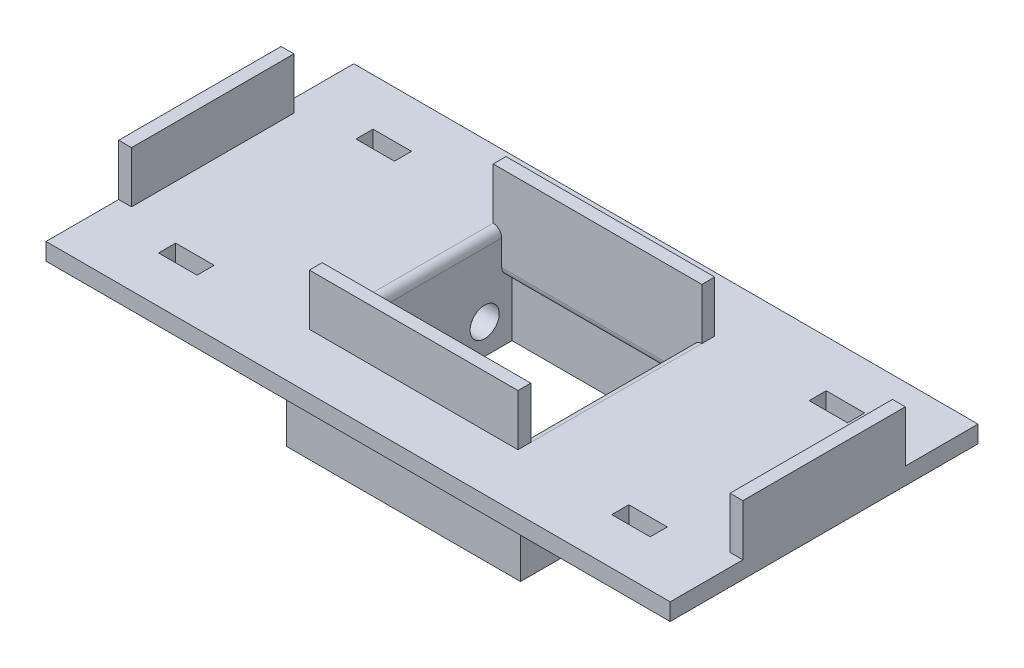
SolidWorks part; units mm, degrees
ref_plane "Front Plane" through (0, 0, 0) normal (0, 0, 1) x (1, 0, 0)
ref_plane "Top Plane" through (0, 0, 0) normal (0, 1, 0) x (1, 0, 0)
ref_plane "Right Plane" through (0, 0, 0) normal (1, 0, 0) x (0, 0, -1)
sketch "Sketch1" plane through (0, 0, 0) normal (0, 1, 0) x (1, 0, 0)
  line L1 (-36.5, 18) -> (36.5, 18)
  line L2 (-36.5, 18) -> (-36.5, -18)
  line L3 (-36.5, -18) -> (36.5, -18)
  line L4 (36.5, 18) -> (36.5, -18)
  line L5 (-36.5, 18) -> (36.5, -18) construction
  line L6 (-36.5, -18) -> (36.5, 18) construction
  point P0 (0, 0)
  dimension "D1" = 36
  dimension "D2" = 73
extrude "Boss-Extrude1" add sketch "Sketch1" along normal blind 2
sketch "Sketch2" plane through (0, 2, 0) normal (0, 1, 0) x (1, 0, 0)
  line L0 (-36.5, 0) -> (36.5, 0) construction
  line L1 (-36.5, 18) -> (-36.5, -18) construction
  line L2 (36.5, -18) -> (36.5, 18) construction
  line L3 (-36.5, 0) -> (-35, 0) construction
  line L4 (-36.5, -9.5) -> (-35, -9.5)
  line L5 (-36.5, -9.5) -> (-36.5, 9.5)
  line L6 (-36.5, 9.5) -> (-35, 9.5)
  line L7 (-35, -9.5) -> (-35, 9.5)
  line L8 (36.5, 9.5) -> (35, 9.5)
  line L9 (36.5, 9.5) -> (36.5, -9.5)
  line L10 (36.5, -9.5) -> (35, -9.5)
  line L11 (35, 9.5) -> (35, -9.5)
  line L12 (35, 0) -> (36.5, 0) construction
  dimension "D1" = 19
  dimension "D2" = 1.5
  dimension "D3" = 1.5
extrude "Boss-Extrude2" add sketch "Sketch2" along normal blind 6
sketch "Sketch3" plane through (0, 0, 0) normal (0, -1, 0) x (1, 0, 0)
  line L0 (-12.2, 11.2) -> (12.2, 11.2)
  line L1 (-13.7, 12.7) -> (13.7, 12.7)
  line L2 (-13.7, 12.7) -> (-13.7, -12.7)
  line L3 (-13.7, -12.7) -> (13.7, -12.7)
  line L4 (13.7, 12.7) -> (13.7, -12.7)
  line L5 (-13.7, 12.7) -> (13.7, -12.7) construction
  line L6 (-13.7, -12.7) -> (13.7, 12.7) construction
  line L7 (12.2, 11.2) -> (12.2, -11.2)
  line L8 (-12.2, -11.2) -> (12.2, -11.2)
  line L9 (-12.2, 11.2) -> (-12.2, -11.2)
  point P0 (0, 0)
  dimension "D1" = 27.4
  dimension "D2" = 25.4
  dimension "D3" = 1.5
extrude "Boss-Extrude3" add sketch "Sketch3" along normal blind 10
sketch "Sketch4" plane through (0, 0, 0) normal (0, -1, 0) x (1, 0, 0)
  line L1 (-12.2, 10) -> (12.2, 10)
  line L2 (-12.2, 10) -> (-12.2, -10)
  line L3 (-12.2, -10) -> (12.2, -10)
  line L4 (12.2, 11.2) -> (-12.2, 11.2)
  line L5 (-12.2, 11.2) -> (-12.2, -11.2)
  line L6 (-12.2, -11.2) -> (12.2, -11.2)
  line L7 (12.2, -11.2) -> (12.2, 11.2)
  line L8 (12.2, 11.2) -> (-12.2, 11.2)
  line L9 (-12.2, 11.2) -> (-12.2, -11.2)
  line L10 (-12.2, -11.2) -> (12.2, -11.2)
  line L11 (12.2, -11.2) -> (12.2, 11.2)
  line L12 (12.2, 10) -> (12.2, -10)
  line L13 (-12.2, 10) -> (12.2, -10) construction
  line L14 (-12.2, -10) -> (12.2, 10) construction
  point P2 (0, 0)
  line M6 (-12.2, 11.2) -> (-12.2, -11.2)
  line M8 (12.2, -11.2) -> (12.2, 11.2)
  dimension "D2" = 20
  dimension "D1" = 0
extrude "Cut-Extrude1" cut sketch "Sketch4" against normal through all contours L3 L1 M6 M8 region at (0, 0, 0)
sketch "Sketch5" plane through (0, 2, 0) normal (0, 1, 0) x (1, 0, 0)
  line L0 (12.2, -10) -> (12.2, 10) construction
  line L1 (-12.2, 10) -> (12.2, 10)
  line L2 (-12.2, 10) -> (-12.2, 11.5)
  line L3 (-12.2, 11.5) -> (12.2, 11.5)
  line L4 (12.2, 10) -> (12.2, 11.5)
  line L5 (-12.2, -10) -> (12.2, -10)
  line L6 (-12.2, -10) -> (-12.2, -11.5)
  line L7 (-12.2, -11.5) -> (12.2, -11.5)
  line L8 (12.2, -10) -> (12.2, -11.5)
  line L9 (-12.2, 10) -> (-12.2, -10) construction
  dimension "D1" = 1.5
  dimension "D2" = 1.5
extrude "Boss-Extrude4" add sketch "Sketch5" along normal blind 6
sketch "Sketch8" plane through (13.7, 0, 0) normal (1, 0, 0) x (0, 0, -1)
  line L0 (0, 0) -> (0, -10) construction
  line L1 (12.7, -10) -> (-12.7, -10) construction
  line L2 (-8, 0) -> (-8, -10) construction
  line L3 (-18, 0) -> (18, 0) construction
  line L4 (8, 0) -> (8, -10) construction
  line L5 (12.7, 0) -> (-12.7, 0) construction
  circle A0 centre (-8, -6.5) radius 1.7
  circle A1 centre (8, -6.5) radius 1.7
  dimension "D3" = 3.4
  dimension "D4" = 3.4
  dimension "D1" = 8
  dimension "D2" = 8
  dimension "D5" = 6.5
  dimension "D6" = 6.5
extrude "Cut-Extrude3" cut sketch "Sketch8" against normal through all
sketch "Sketch9" plane through (0, 2, 0) normal (0, 1, 0) x (1, 0, 0)
  line L0 (-36.5, 11.5) -> (36.5, 11.5) construction
  line L1 (-36.5, 18) -> (-36.5, 9.5) construction
  line L2 (36.5, 9.5) -> (36.5, 18) construction
  line L3 (-36.5, -11.5871) -> (36.5, -11.5871) construction
  line L4 (-36.5, -9.5) -> (-36.5, -18) construction
  line L5 (36.5, -18) -> (36.5, -9.5) construction
  line L6 (26.5, 11.5) -> (26.5, -11.5871) construction
  line L7 (-26.5, 11.5) -> (-26.5, -11.5871) construction
  line L8 (-36.5, 9.5) -> (-36.5, -9.5) construction
  line L10 (-28.75, 12.5) -> (-24.25, 12.5)
  line L11 (-28.75, 12.5) -> (-28.75, 10.5)
  line L12 (-28.75, 10.5) -> (-24.25, 10.5)
  line L13 (-24.25, 12.5) -> (-24.25, 10.5)
  line L14 (-28.75, 12.5) -> (-24.25, 10.5) construction
  line L15 (-28.75, 10.5) -> (-24.25, 12.5) construction
  line L16 (24.25, 12.5) -> (28.75, 12.5)
  line L17 (24.25, 12.5) -> (24.25, 10.5)
  line L18 (24.25, 10.5) -> (28.75, 10.5)
  line L19 (28.75, 12.5) -> (28.75, 10.5)
  line L20 (24.25, 12.5) -> (28.75, 10.5) construction
  line L21 (24.25, 10.5) -> (28.75, 12.5) construction
  line L22 (24.25, -10.5871) -> (28.75, -10.5871)
  line L23 (24.25, -10.5871) -> (24.25, -12.5871)
  line L24 (24.25, -12.5871) -> (28.75, -12.5871)
  line L25 (28.75, -10.5871) -> (28.75, -12.5871)
  line L26 (24.25, -10.5871) -> (28.75, -12.5871) construction
  line L27 (24.25, -12.5871) -> (28.75, -10.5871) construction
  line L28 (-28.75, -10.5871) -> (-24.25, -10.5871)
  line L29 (-28.75, -10.5871) -> (-28.75, -12.5871)
  line L30 (-28.75, -12.5871) -> (-24.25, -12.5871)
  line L31 (-24.25, -10.5871) -> (-24.25, -12.5871)
  line L32 (-28.75, -10.5871) -> (-24.25, -12.5871) construction
  line L33 (-28.75, -12.5871) -> (-24.25, -10.5871) construction
  dimension "D1" = 10
  dimension "D2" = 10
  dimension "D3" = 4.5
  dimension "D4" = 2
extrude "Cut-Extrude4" cut sketch "Sketch9" against normal through all
sketch "Sketch10" plane through (0, 0, 0) normal (0, -1, 0) x (1, 0, 0)
  line L4 (-12.2, 11.2) -> (-12.2, 10)
  line L5 (-12.2, 10) -> (12.2, 10)
  line L6 (12.2, 10) -> (12.2, 11.2)
  line L7 (12.2, 11.2) -> (-12.2, 11.2)
  line L8 (-12.2, 11.2) -> (-12.2, 10)
  line L9 (-12.2, 10) -> (12.2, 10)
  line L10 (12.2, 10) -> (12.2, 11.2)
  line L11 (12.2, 11.2) -> (-12.2, 11.2)
  line L12 (12.2, -10) -> (-12.2, -10)
  line L13 (-12.2, -10) -> (-12.2, -11.2)
  line L14 (-12.2, -11.2) -> (12.2, -11.2)
  line L15 (12.2, -11.2) -> (12.2, -10)
  line L16 (12.2, -10) -> (-12.2, -10)
  line L17 (-12.2, -10) -> (-12.2, -11.2)
  line L18 (-12.2, -11.2) -> (12.2, -11.2)
  line L19 (12.2, -11.2) -> (12.2, -10)
  dimension "D1" = 0
  dimension "D2" = 0
extrude "Boss-Extrude5" add sketch "Sketch10" along normal blind 3
fillet "Fillet1" radius 1 1 edges at (0, -3, 10)
fillet "Fillet2" radius 1 1 edges at (0, -3, -10)
sketch "Sketch11" plane through (12.2, 0, 0) normal (-1, 0, 0) x (0, 0, 1)
  line L8 (-10, 2) -> (-10, -2)
  line L9 (-11, -3) -> (-11.2, -3)
  line L10 (-11.2, -3) -> (-11.2, -10)
  line L11 (-11.2, -10) -> (11.2, -10)
  line L12 (11.2, -10) -> (11.2, -3)
  line L13 (11.2, -3) -> (11, -3)
  line L14 (10, -2) -> (10, 2)
  line L15 (10, 2) -> (-10, 2)
  line L16 (-10, 2) -> (-10, -2)
  line L17 (-11, -3) -> (-11.2, -3)
  line L18 (-11.2, -3) -> (-11.2, -10)
  line L19 (-11.2, -10) -> (11.2, -10)
  line L20 (11.2, -10) -> (11.2, -3)
  line L21 (11.2, -3) -> (11, -3)
  line L22 (10, -2) -> (10, 2)
  line L23 (10, 2) -> (-10, 2)
  circle A0 centre (8, -6.5) radius 1.7 construction
  circle A1 centre (-8, -6.5) radius 1.7 construction
  arc A2 (-11, -3) -> (-10, -2) centre (-11, -2) ccw
  arc A3 (10, -2) -> (11, -3) centre (11, -2) ccw
  arc A4 (-11, -3) -> (-10, -2) centre (-11, -2) ccw
  arc A5 (10, -2) -> (11, -3) centre (11, -2) ccw
  circle A6 centre (8, -6.5) radius 1.7
  circle A7 centre (-8, -6.5) radius 1.7
  dimension "D1" = 0
extrude "Boss-Extrude7" add sketch "Sketch11" along normal blind 1
sketch "Sketch12" plane through (-12.2, 0, 0) normal (1, 0, 0) x (0, 0, -1)
  line L8 (11.2, -3) -> (11, -3)
  line L9 (10, -2) -> (10, 2)
  line L10 (10, 2) -> (-10, 2)
  line L11 (-10, 2) -> (-10, -2)
  line L12 (-11, -3) -> (-11.2, -3)
  line L13 (-11.2, -3) -> (-11.2, -10)
  line L14 (-11.2, -10) -> (11.2, -10)
  line L15 (11.2, -10) -> (11.2, -3)
  line L16 (11.2, -3) -> (11, -3)
  line L17 (10, -2) -> (10, 2)
  line L18 (10, 2) -> (-10, 2)
  line L19 (-10, 2) -> (-10, -2)
  line L20 (-11, -3) -> (-11.2, -3)
  line L21 (-11.2, -3) -> (-11.2, -10)
  line L22 (-11.2, -10) -> (11.2, -10)
  line L23 (11.2, -10) -> (11.2, -3)
  circle A0 centre (-8, -6.5) radius 1.7 construction
  circle A1 centre (8, -6.5) radius 1.7 construction
  arc A2 (10, -2) -> (11, -3) centre (11, -2) ccw
  arc A3 (-11, -3) -> (-10, -2) centre (-11, -2) ccw
  arc A4 (10, -2) -> (11, -3) centre (11, -2) ccw
  arc A5 (-11, -3) -> (-10, -2) centre (-11, -2) ccw
  circle A6 centre (-8, -6.5) radius 1.7
  circle A7 centre (8, -6.5) radius 1.7
  dimension "D1" = 0
extrude "Boss-Extrude8" add sketch "Sketch12" along normal blind 1
fillet "Fillet3" radius 1 2 edges at (11.2, 2, 0) (-11.2, 2, 0)
